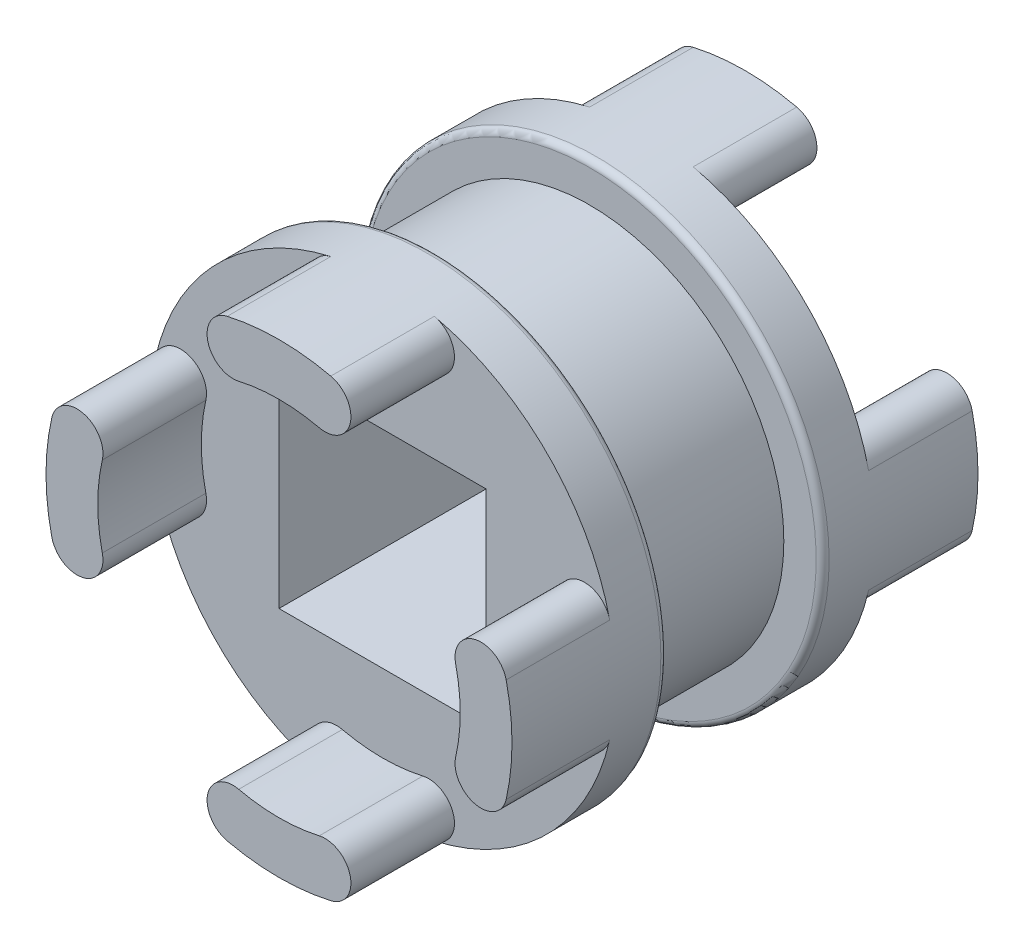
SolidWorks part; units mm, degrees
ref_plane "Front Plane" through (0, 0, 0) normal (0, 0, 1) x (1, 0, 0)
ref_plane "Top Plane" through (0, 0, 0) normal (0, 1, 0) x (1, 0, 0)
ref_plane "Right Plane" through (0, 0, 0) normal (1, 0, 0) x (0, 0, -1)
sketch "Sketch2" plane through (0, 0, 0) normal (1, 0, 0) x (0, 0, -1)
  line L0 (-5, 0) -> (-5, 9)
  line L1 (-5, 9) -> (-3, 9)
  line L2 (-3, 9) -> (-3, 7.5)
  line L3 (-3, 7.5) -> (3, 7.5)
  line L4 (0, -20.9183) -> (0, 20.9183) construction
  line L5 (-5, 0) -> (5, 0)
  line L6 (3, 9) -> (3, 7.5)
  line L7 (5, 9) -> (3, 9)
  line L8 (5, 0) -> (5, 9)
  line L9 (0, 0) -> (15.424, 0)
  line L10 (55, 0) -> (-55, 0) construction
  point P6 (0, 0)
  point P10 (0, 0)
  point P13 (0, 0)
  point P14 (0, 7.5)
  dimension "D1" = 9
  dimension "D2" = 1.5
  dimension "D3" = 6
  dimension "D4" = 2
revolve "Revolve1" add sketch "Sketch2" angle 360 about L9 region at (0, 4.0833, 2.6111) region at (0, 4.0833, -2.6111)
fillet "Fillet2" radius 0.25 2 edges at (9, 0, -3) (9, 0, 3)
sketch "Sketch3" plane through (0, 0, -5) normal (0, 0, -1) x (-1, 0, 0)
  line L0 (0, 0) -> (0, 18.3802) construction
  line L1 (0, 55) -> (0, -55) construction
  line L2 (2, 8.775) -> (1.5556, 6.825) construction
  arc A0 (0, 9) -> (2, 8.775) centre (0, 0) cw
  arc A1 (0, 7) -> (1.5556, 6.825) centre (0, 0) cw
  circle A2 centre (1.7778, 7.8) radius 1
  arc A3 (0, 7) -> (-1.5556, 6.825) centre (0, 0) ccw
  arc A4 (0, 9) -> (-2, 8.775) centre (0, 0) ccw
  circle A5 centre (-1.7778, 7.8) radius 1
  dimension "D1" = 9
  dimension "D2" = 2
  dimension "D3" = 2
extrude "Boss-Extrude1" add sketch "Sketch3" along normal blind 4 contours A4 A5 A3 A1 A2 A0 | A5 | A2 region at (0, 8.0371, -5) region at (-1.7778, 7.8, -5) region at (1.7778, 7.8, -5)
pattern_circular "CirPattern1" count 4 over 360 about axis through (0, 0, 5) along (0, 0, 1) of "Boss-Extrude1"
mirror "Mirror1" about plane through (0, 0, 0) normal (0, 0, 1) of "CirPattern1"
sketch "Sketch4" plane through (0, 0, -5) normal (0, 0, -1) x (-1, 0, 0)
  line L1 (-4, -4) -> (4, -4)
  line L2 (-4, -4) -> (-4, 4)
  line L3 (-4, 4) -> (4, 4)
  line L4 (4, -4) -> (4, 4)
  line L5 (-4, -4) -> (4, 4) construction
  line L6 (-4, 4) -> (4, -4) construction
  point P0 (0, 0)
  dimension "D1" = 8
extrude "Cut-Extrude1" cut sketch "Sketch4" against normal up to next
